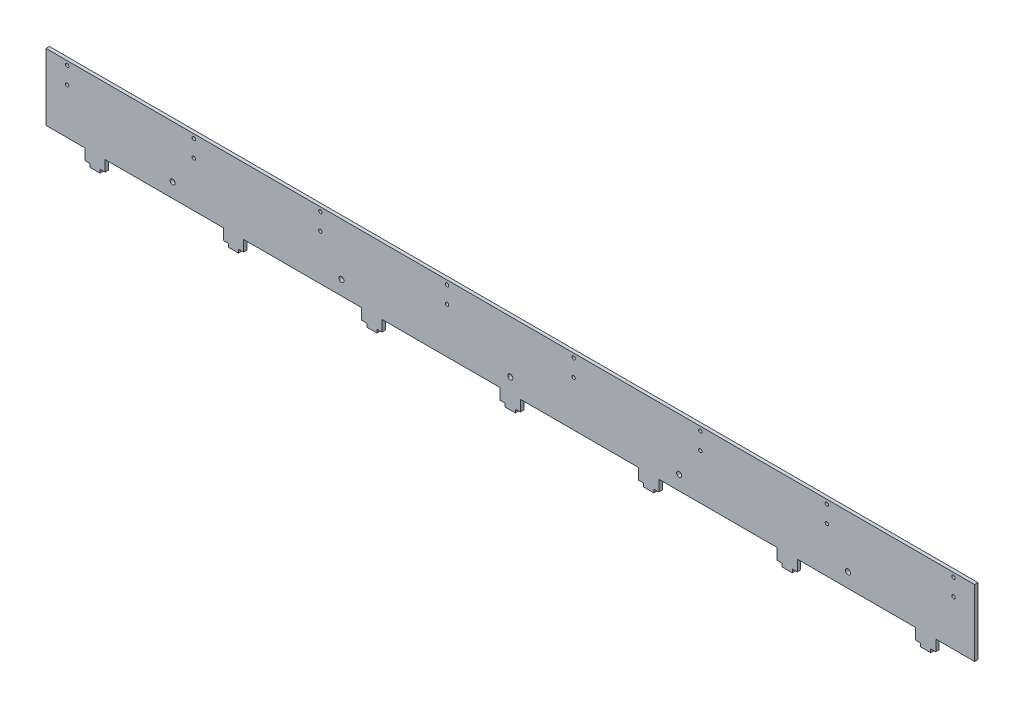
SolidWorks part; units mm, degrees
ref_plane "Спереди" through (0, 0, 0) normal (0, 0, 1) x (1, 0, 0)
ref_plane "Сверху" through (0, 0, 0) normal (0, 1, 0) x (1, 0, 0)
ref_plane "Справа" through (0, 0, 0) normal (1, 0, 0) x (0, 0, -1)
sketch "Эскиз1" plane through (0, 0, 0) normal (0, 0, 1) x (1, 0, 0)
  line L1 (-550, -46) -> (550, -46)
  line L2 (-550, -46) -> (-550, 46)
  line L3 (-550, 46) -> (550, 46)
  line L4 (550, -46) -> (550, 46)
  line L5 (0, 46) -> (0, -46) construction
  line L6 (-550, 0) -> (550, 0) construction
  point P0 (0, 0)
  dimension "D1" = 92
  dimension "D2" = 1100
extrude "Бобышка-Вытянуть1" add sketch "Эскиз1" along normal mid plane 4
sketch "Эскиз2" plane through (0, 0, 2) normal (0, 0, 1) x (1, 0, 0)
  line L0 (-550, -46) -> (550, -46) construction
  line L1 (-550, -46) -> (-504, -46)
  line L2 (-550, -46) -> (-550, -33)
  line L3 (-550, -33) -> (-504, -33)
  line L4 (-504, -46) -> (-504, -33)
  line L5 (550, -46) -> (504, -46)
  line L6 (550, -46) -> (550, -33)
  line L7 (550, -33) -> (504, -33)
  line L8 (504, -46) -> (504, -33)
  line L9 (-480, -33) -> (-340, -33)
  line L10 (-480, -33) -> (-480, -46)
  line L11 (-480, -46) -> (-340, -46)
  line L12 (-340, -33) -> (-340, -46)
  line L14 (-316, -33) -> (-176, -33)
  line L15 (-316, -33) -> (-316, -46)
  line L16 (-316, -46) -> (-176, -46)
  line L17 (-176, -33) -> (-176, -46)
  line L18 (-152, -33) -> (-12, -33)
  line L19 (-152, -33) -> (-152, -46)
  line L20 (-152, -46) -> (-12, -46)
  line L21 (-12, -33) -> (-12, -46)
  line L22 (12, -33) -> (152, -33)
  line L23 (12, -33) -> (12, -46)
  line L24 (12, -46) -> (152, -46)
  line L25 (152, -33) -> (152, -46)
  line L26 (176, -33) -> (316, -33)
  line L27 (176, -33) -> (176, -46)
  line L28 (176, -46) -> (316, -46)
  line L29 (316, -33) -> (316, -46)
  line L30 (340, -33) -> (480, -33)
  line L31 (340, -33) -> (340, -46)
  line L32 (340, -46) -> (480, -46)
  line L33 (480, -33) -> (480, -46)
  point P20 (-316, -39.5)
  point P25 (-152, -39.5)
  point P26 (152, -39.5)
  point P39 (340, -39.5)
  dimension "D1" = 13
  dimension "D5" = 24
  dimension "D6" = 140
  dimension "D7" = 24
  dimension "D2" = 24
  dimension "D3" = 140
  dimension "D4" = 140
  dimension "D8" = 24
  dimension "D9" = 140
  dimension "D10" = 24
  dimension "D11" = 140
  dimension "D12" = 24
  dimension "D13" = 140
  dimension "D14" = 24
extrude "Вырез-Вытянуть1" cut sketch "Эскиз2" against normal through all
sketch "Эскиз3" plane through (0, 0, 2) normal (0, 0, 1) x (1, 0, 0)
  line L0 (550, 46) -> (-550, 46) construction
  line L1 (-550, 46) -> (-550, -33) construction
  circle A0 centre (-525, 41) radius 2
  circle A1 centre (-525, 21) radius 2
  dimension "D1" = 4
  dimension "D2" = 5
  dimension "D3" = 20
  dimension "D4" = 25
extrude "Вырез-Вытянуть2" cut sketch "Эскиз3" against normal through all
pattern_linear "Линейный массив1" count 8 spacing 150 along (1, 0, 0) of "Вырез-Вытянуть2"
sketch "Эскиз4" plane through (0, 0, -2) normal (0, 0, -1) x (-1, 0, 0)
  circle A1 centre (-400, -16) radius 3
  circle A2 centre (-400, -16) radius 3
  dimension "D1" = 0
extrude "Вырез-Вытянуть3" cut sketch "Эскиз4" against normal through all
pattern_linear "Линейный массив2" count 5 spacing 200 along (-1, 0, 0) of "Вырез-Вытянуть3"
sketch "Эскиз5" plane through (0, -46, 0) normal (0, -1, 0) x (1, 0, 0)
  line L0 (492, -2) -> (492, 2) construction
  line L1 (480, 2) -> (504, 2) construction
  line L2 (328, -2) -> (328, 2) construction
  line L3 (316, -2) -> (340, -2) construction
  line L4 (504, 2) -> (480, 2)
  line L5 (480, 2) -> (480, -2)
  line L6 (480, -2) -> (504, -2)
  line L7 (504, -2) -> (504, 2)
  line L8 (498, 2) -> (486, 2)
  line L9 (486, 2) -> (486, -2)
  line L10 (486, -2) -> (498, -2)
  line L11 (498, -2) -> (498, 2)
  line L12 (316, 2) -> (340, 2) construction
  line L13 (164, -2) -> (164, 2) construction
  line L14 (316, -2) -> (340, -2)
  line L15 (340, -2) -> (340, 2)
  line L16 (340, 2) -> (316, 2)
  line L17 (316, 2) -> (316, -2)
  line L18 (322, -2) -> (334, -2)
  line L19 (334, -2) -> (334, 2)
  line L20 (334, 2) -> (322, 2)
  line L21 (322, 2) -> (322, -2)
  line L22 (152, -2) -> (176, -2) construction
  line L23 (152, 2) -> (176, 2) construction
  line L24 (0, -2) -> (0, 2) construction
  line L25 (176, 2) -> (152, 2)
  line L26 (152, 2) -> (152, -2)
  line L27 (152, -2) -> (176, -2)
  line L28 (176, -2) -> (176, 2)
  line L29 (170, 2) -> (158, 2)
  line L30 (158, 2) -> (158, -2)
  line L31 (158, -2) -> (170, -2)
  line L32 (170, -2) -> (170, 2)
  line L33 (-12, -2) -> (12, -2) construction
  line L34 (-12, 2) -> (12, 2) construction
  line L36 (-12, -2) -> (12, -2)
  line L37 (12, -2) -> (12, 2)
  line L38 (12, 2) -> (-12, 2)
  line L39 (-12, 2) -> (-12, -2)
  line L40 (-6, -2) -> (6, -2)
  line L41 (6, -2) -> (6, 2)
  line L42 (6, 2) -> (-6, 2)
  line L43 (-6, 2) -> (-6, -2)
  line L44 (-480, 2) -> (-504, 2) construction
  line L46 (-504, -2) -> (-480, -2) construction
  line L48 (-316, 2) -> (-340, 2) construction
  line L50 (-340, -2) -> (-316, -2) construction
  line L52 (-152, 2) -> (-176, 2) construction
  line L54 (-176, -2) -> (-152, -2) construction
  line L56 (-486, 2) -> (-498, 2)
  line L57 (-498, 2) -> (-498, -2)
  line L58 (-498, -2) -> (-486, -2)
  line L59 (-486, -2) -> (-486, 2)
  line L60 (-322, 2) -> (-334, 2)
  line L61 (-334, 2) -> (-334, -2)
  line L62 (-334, -2) -> (-322, -2)
  line L63 (-322, -2) -> (-322, 2)
  line L64 (-158, 2) -> (-170, 2)
  line L65 (-170, 2) -> (-170, -2)
  line L66 (-170, -2) -> (-158, -2)
  line L67 (-158, -2) -> (-158, 2)
  line L68 (-492, -2) -> (-492, 2) construction
  line L69 (-504, 2) -> (-480, 2) construction
  line L70 (-328, -2) -> (-328, 2) construction
  line L71 (-340, 2) -> (-316, 2) construction
  line L72 (-164, -2) -> (-164, 2) construction
  line L73 (-176, 2) -> (-152, 2) construction
  point P85 (-334, 0)
  dimension "D2" = 12
  dimension "D4" = 12
  dimension "D6" = 12
  dimension "D8" = 12
  dimension "D9" = 12
  dimension "D10" = 12
  dimension "D11" = 12
  dimension "D1" = 0
  dimension "D3" = 0
  dimension "D5" = 0
  dimension "D7" = 0
extrude "Бобышка-Вытянуть2" add sketch "Эскиз5" along normal blind 4
equation "\"D7@Эскиз2\"=\"D5@Эскиз2\""
equation "\"D2@Эскиз2\"=\"D5@Эскиз2\""
equation "\"D3@Эскиз2\"=\"D6@Эскиз2\""
equation "\"D4@Эскиз2\"=\"D6@Эскиз2\""
equation "\"D8@Эскиз2\"=\"D5@Эскиз2\""
equation "\"D9@Эскиз2\"=\"D6@Эскиз2\""
equation "\"D10@Эскиз2\"=\"D5@Эскиз2\""
equation "\"D11@Эскиз2\"=\"D6@Эскиз2\""
equation "\"D12@Эскиз2\"=\"D5@Эскиз2\""
equation "\"D13@Эскиз2\"=\"D6@Эскиз2\""
equation "\"D14@Эскиз2\"=\"D5@Эскиз2\""
